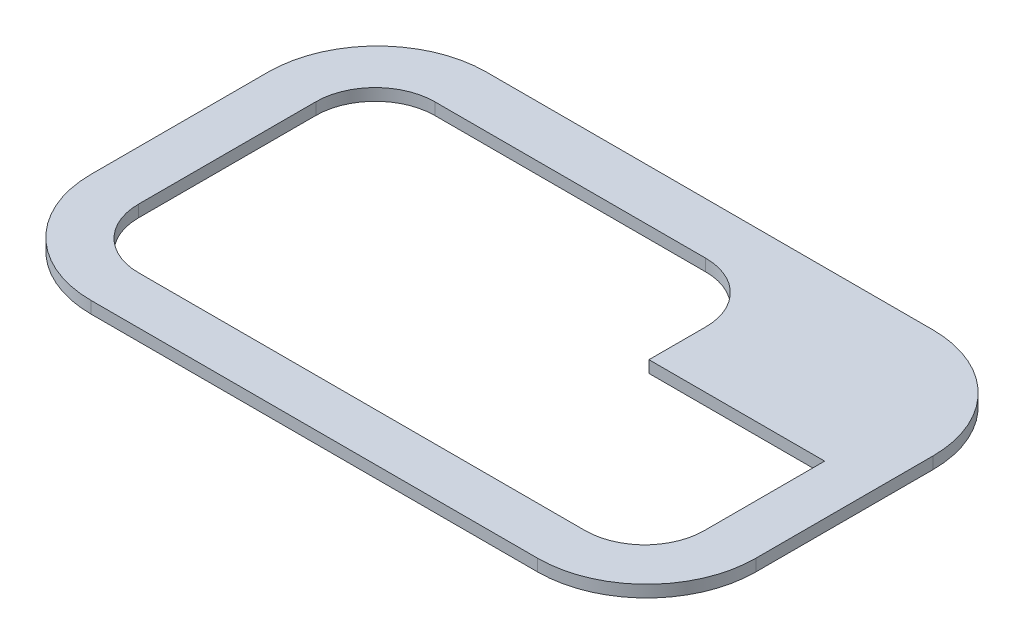
SolidWorks part; units mm, degrees
ref_plane "Front Plane" through (0, 0, 0) normal (0, 0, 1) x (1, 0, 0)
ref_plane "Top Plane" through (0, 0, 0) normal (0, 1, 0) x (1, 0, 0)
ref_plane "Right Plane" through (0, 0, 0) normal (1, 0, 0) x (0, 0, -1)
sketch "Sketch1" plane through (0, 0, 0) normal (0, 1, 0) x (1, 0, 0)
  line L0 (19.3997, -140.4657) -> (186.9882, -140.4657) construction
  line L1 (-19.7342, 34.7624) -> (205.2958, 34.7624)
  line L2 (-74.7342, -20.2376) -> (-74.7342, -109.4976)
  line L3 (-19.7342, -164.4976) -> (205.2958, -164.4976)
  line L4 (260.2958, -20.2376) -> (260.2958, -109.4976)
  line L5 (-19.7644, 8.7943) -> (116.7356, 8.7943)
  line L6 (-49.7644, -21.2057) -> (-49.7644, -110.4657)
  line L7 (-19.7644, -140.4657) -> (146.7356, -140.4657)
  line L8 (146.7356, -21.2057) -> (146.7356, -49.8057)
  line L9 (146.7356, -49.8057) -> (235.2656, -49.8057)
  line L11 (146.7356, -140.4657) -> (205.2656, -140.4657)
  line L12 (235.2656, -49.8057) -> (235.2656, -110.4657)
  arc A0 (-74.7342, -109.4976) -> (-19.7342, -164.4976) centre (-19.7342, -109.4976) ccw
  arc A1 (205.2958, -164.4976) -> (260.2958, -109.4976) centre (205.2958, -109.4976) ccw
  arc A2 (205.2958, 34.7624) -> (260.2958, -20.2376) centre (205.2958, -20.2376) cw
  arc A3 (-19.7342, 34.7624) -> (-74.7342, -20.2376) centre (-19.7342, -20.2376) ccw
  arc A4 (205.2656, -140.4657) -> (235.2656, -110.4657) centre (205.2656, -110.4657) ccw
  arc A5 (-49.7644, -110.4657) -> (-19.7644, -140.4657) centre (-19.7644, -110.4657) ccw
  arc A6 (116.7356, 8.7943) -> (146.7356, -21.2057) centre (116.7356, -21.2057) cw
  arc A7 (-19.7644, 8.7943) -> (-49.7644, -21.2057) centre (-19.7644, -21.2057) ccw
  point P6 (-74.7342, -164.4976)
  point P11 (260.2958, 34.7624)
  point P14 (-74.7342, 34.7624)
  point P24 (235.2656, -140.4657)
  point P27 (-49.7644, -140.4657)
  point P32 (-49.7644, 8.7943)
  dimension "D3" = 55
  dimension "D8" = 30
  dimension "D1" = 335.03
  dimension "D2" = 199.26
  dimension "D4" = 149.26
  dimension "D5" = 196.5
  dimension "D6" = 88.53
  dimension "D7" = 90.66
extrude "Boss-Extrude1" add sketch "Sketch1" along normal blind 6
